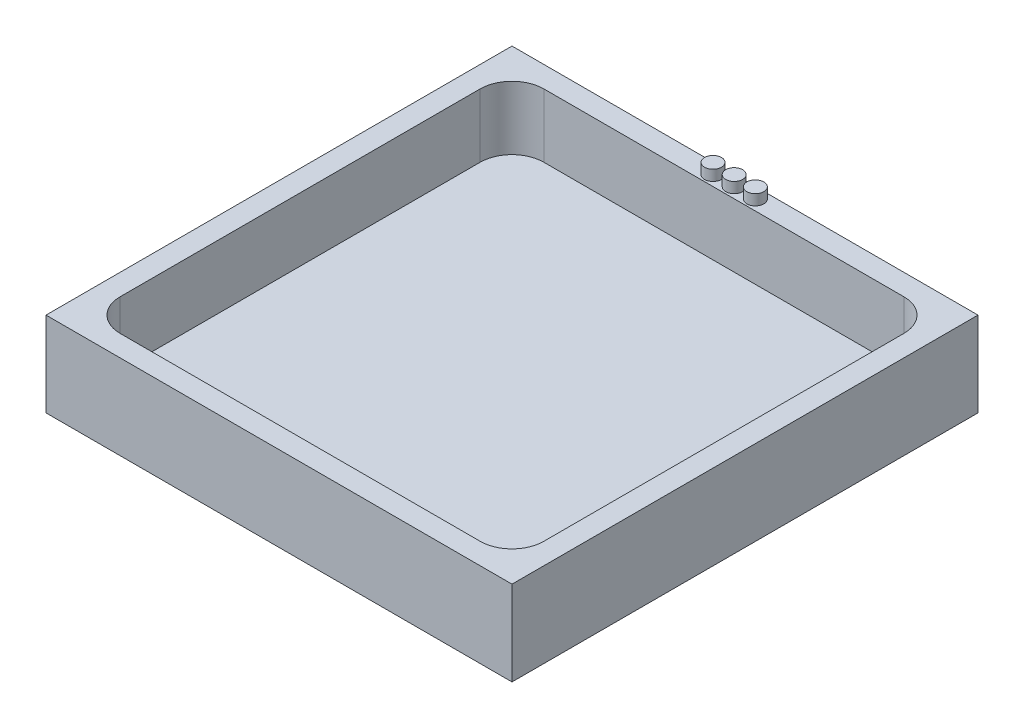
SolidWorks part; units mm, degrees
ref_plane "Front Plane" through (0, 0, 0) normal (0, 0, 1) x (1, 0, 0)
ref_plane "Top Plane" through (0, 0, 0) normal (0, 1, 0) x (1, 0, 0)
ref_plane "Right Plane" through (0, 0, 0) normal (1, 0, 0) x (0, 0, -1)
sketch "Sketch1" plane through (0, 0, 0) normal (0, 1, 0) x (1, 0, 0)
  line L1 (-10, -10) -> (10, -10)
  line L2 (-10, -10) -> (-10, 10)
  line L3 (-10, 10) -> (10, 10)
  line L4 (10, -10) -> (10, 10)
  line L5 (-10, -10) -> (10, 10) construction
  line L6 (-10, 10) -> (10, -10) construction
  line L7 (-11, -11) -> (11, -11)
  line L8 (-11, -11) -> (-11, 11)
  line L9 (-11, 11) -> (11, 11)
  line L10 (11, -11) -> (11, 11)
  line L11 (-11, -11) -> (11, 11) construction
  line L12 (-11, 11) -> (11, -11) construction
  point P0 (0, 0)
  point P6 (0, 0)
  dimension "D1" = 20
  dimension "D2" = 20
  dimension "D3" = 22
  dimension "D4" = 22
extrude "Boss-Extrude2" add sketch "Sketch1" along normal blind 1 contours L3 L4 L1 L2
extrude "Boss-Extrude3" add sketch "Sketch1<6>" along normal blind 4
sketch "Sketch1<6>" plane through (0, 0, 0) normal (0, 1, 0) x (1, 0, 0) same geometry as "Sketch1"
sketch "Sketch2" plane through (0, 4, 0) normal (0, 1, 0) x (1, 0, 0)
  line L0 (0, -2.2) -> (0, 2.2) construction
  circle A0 centre (0, 10.4902) radius 0.4
  circle A1 centre (1, 10.4902) radius 0.4
  circle A2 centre (-1, 10.4902) radius 0.4
  dimension "D1" = 1
  dimension "D2" = 1
extrude "Boss-Extrude4" add sketch "Sketch2" along normal blind 0.5
fillet "Fillet1" radius 1.5 4 edges at (10, 2.5, -10) (-10, 2.5, -10) (-10, 2.5, 10) (10, 2.5, 10)
